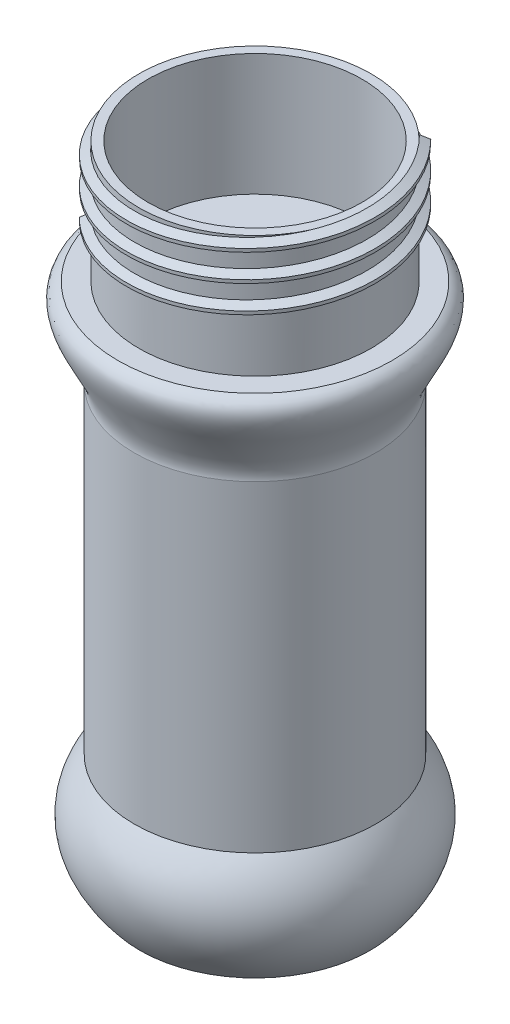
SolidWorks part; units mm, degrees
ref_plane "Спереди" through (0, 0, 0) normal (0, 0, 1) x (1, 0, 0)
ref_plane "Сверху" through (0, 0, 0) normal (0, 1, 0) x (1, 0, 0)
ref_plane "Справа" through (0, 0, 0) normal (1, 0, 0) x (0, 0, -1)
sketch "Эскиз1" plane through (0, 0, 0) normal (0, 1, 0) x (1, 0, 0)
  circle A0 centre (0, 0) radius 20.25
  circle A1 centre (0, -20.25) radius 7.2898 construction
ref_plane "Плоскость1" through (0, 0, 20.25) normal (1, 0, 0) x (0, 0, -1)
sketch "Эскиз2" plane through (0, 0, 20.25) normal (1, 0, 0) x (0, 0, -1)
  line L0 (20.25, -2.8848) -> (20.25, 13.7152)
  line L1 (3.25, -2.8848) -> (20.25, -2.8848)
  line L2 (20.25, 13.7152) -> (2.4, 13.7152)
  spline S0 degree 2 poles (3.25, -2.8848) (-4.1403, 5.7214) (2.4, 13.7152) knots 0 0 0 1 1 1
sweep "По траектории5" add profiles "Эскиз2" path "Эскиз1"
sketch "Эскиз3" plane through (0, 13.7152, 0) normal (0, 1, 0) x (1, 0, 0)
  circle A0 centre (0, 0) radius 17.85
extrude "Бобышка-Вытянуть1" add sketch "Эскиз3" along normal blind 47.5
sketch "Эскиз4" plane through (0, 0, 20.25) normal (1, 0, 0) x (0, 0, -1)
  line L0 (2.4, 13.7152) -> (2.4, 61.2152) construction
  line L1 (2.4, 61.2152) -> (2.4, 74.2152) construction
  line L2 (2.4, 61.2152) -> (38.1, 61.2152) construction
  line L3 (20.25, 61.2152) -> (20.25, 74.2152)
  line L4 (20.25, 74.2152) -> (0, 74.2152)
  line L5 (20.25, 61.2152) -> (2.4, 61.2152)
  line L6 (2.4, 61.2152) -> (2.3956, 61.1791)
  spline S0 degree 3 poles (2.4, 61.2152) (3.0081, 65.1516) (-4.6864, 72.1185) (0, 74.2152) knots 0 0 0 0 1 1 1 1
ref_plane "Плоскость2" through (0, 66.2152, 0) normal (0, 1, 0) x (1, 0, 0)
revolve "Повернуть1" add sketch "Эскиз4" angle 360 about L3 region at (0, 67.9669, 10.0366)
sketch "Эскиз5" plane through (0, 74.2152, 0) normal (0, 1, 0) x (1, 0, 0)
  circle A0 centre (0, 0) radius 15.8
  circle A1 centre (0, 0) radius 17.15
extrude "Бобышка-Вытянуть2" add sketch "Эскиз5" along normal blind 18
sketch "Эскиз8" plane through (0, 92.2152, 0) normal (0, 1, 0) x (1, 0, 0)
  circle A0 centre (0, 0) radius 17.15
curve "Спираль1" pitch 4 height 10 radius 17.15 centre (0, 92.2152, 0) axis (0, -1, 0) start towards (0.7071, 0, -0.7071)
ref_plane "Плоскость4" through (12.1269, 92.2152, -12.1269) normal (0.7066, -0.0371, 0.7066) x (0.7056, -0.037, -0.7076)
sketch "Эскиз9" plane through (12.1269, 92.2152, -12.1269) normal (0.7066, -0.0371, 0.7066) x (0.7056, -0.037, -0.7076)
  line L0 (0, 0.8) -> (0, -0.8)
  line L1 (0, 0) -> (1.2, 0) construction
  line L2 (1.2, -0.25) -> (0, -0.8)
  line L3 (1.2, -0.25) -> (1.2, 0.25)
  line L4 (1.2, 0.25) -> (0, 0.8)
  circle A0 centre (0, 0) radius 0.8 construction
  circle A1 centre (1.2, 0) radius 0.25 construction
sweep "По траектории6" add profiles "Эскиз9" path "Спираль1"
